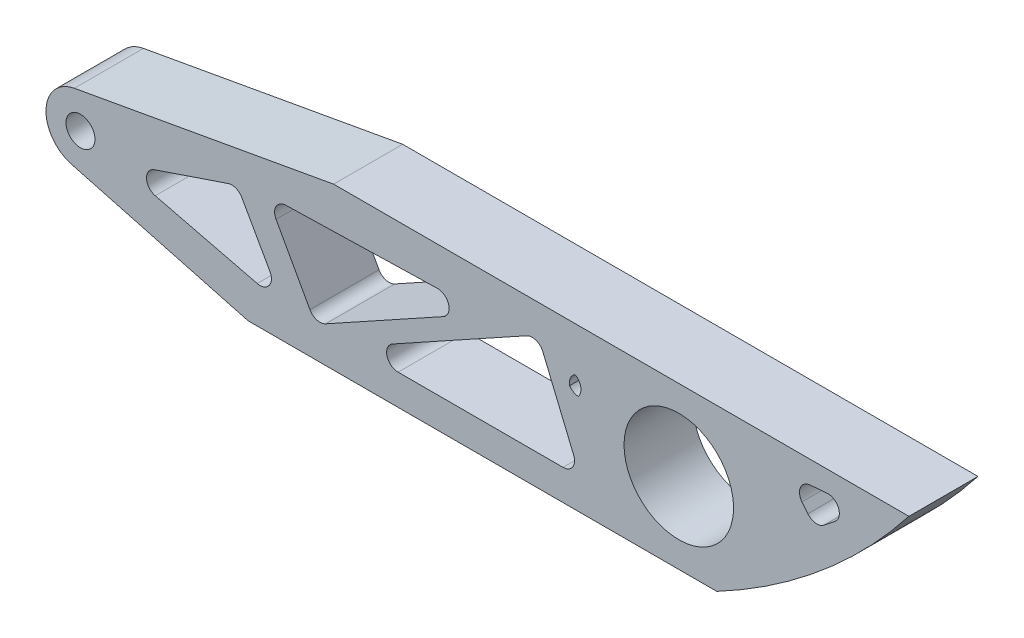
SolidWorks part; units mm, degrees
ref_plane "Front Plane" through (0, 0, 0) normal (0, 0, 1) x (1, 0, 0)
ref_plane "Top Plane" through (0, 0, 0) normal (0, 1, 0) x (1, 0, 0)
ref_plane "Right Plane" through (0, 0, 0) normal (1, 0, 0) x (0, 0, -1)
sketch "Sketch1" plane through (0, 0, 0) normal (0, 0, 1) x (1, 0, 0)
  line L1 (120.65, 22.225) -> (-120.65, 22.225)
  line L2 (120.65, 22.225) -> (120.65, -22.225)
  line L3 (120.65, -22.225) -> (-120.65, -22.225)
  line L4 (-120.65, 22.225) -> (-120.65, -22.225)
  line L5 (120.65, 22.225) -> (-120.65, -22.225) construction
  line L6 (120.65, -22.225) -> (-120.65, 22.225) construction
  point P0 (0, 0)
  dimension "D1" = 241.3
  dimension "D2" = 44.45
extrude "Boss-Extrude1" add sketch "Sketch1" along normal blind 19.06
sketch "Sketch3" plane through (0, 0, 19.06) normal (0, 0, 1) x (1, 0, 0)
  line L0 (0, 0) -> (-120.65, 0) construction
  line L1 (-120.65, 22.225) -> (-120.65, -22.225) construction
  circle A0 centre (-107.95, 0) radius 4
  dimension "D2" = 8
  dimension "D1" = 12.7
extrude "Cut-Extrude1" cut sketch "Sketch3" against normal through all
sketch "Sketch5" plane through (0, 0, 19.06) normal (0, 0, 1) x (1, 0, 0)
  line L0 (-120.65, -22.225) -> (120.65, -22.225) construction
  line L1 (-110.4107, -9.2017) -> (-61.7102, -22.225)
  line L2 (-109.6341, 9.3749) -> (-38.1, 22.225)
  line L3 (120.65, 22.225) -> (-120.65, 22.225) construction
  line L4 (-38.1, 22.225) -> (-120.65, 22.225)
  line L5 (-120.65, 22.225) -> (-120.65, -22.225)
  line L6 (-120.65, -22.225) -> (-61.7102, -22.225)
  line L7 (120.65, 22.225) -> (120.65, -22.225)
  line L8 (120.65, -22.225) -> (67.6371, -22.225)
  arc A0 (67.6371, -22.225) -> (120.65, 22.225) centre (-9.5799, 123.7049) ccw
  arc A2 (-109.6341, 9.3749) -> (-110.4107, -9.2017) centre (-107.95, 0) ccw
  point P15 (-38.5913, 22.225)
  line M3 (-120.65, 22.225) -> (-120.65, -22.225)
  line M4 (-120.65, -22.225) -> (120.65, -22.225)
  line M5 (120.65, -22.225) -> (120.65, 22.225)
  line M6 (120.65, 22.225) -> (-120.65, 22.225)
  dimension "D1" = 165.1
  dimension "D2" = 19.05
  dimension "D3" = 82.55
extrude "Cut-Extrude2" cut sketch "Sketch5" against normal through all contours A0 L8 M5 | A2 L2 L1 M6 M3 M4 region at (-86.3027, -16.6191, 19.06) region at (104.3043, -8.4634, 19.06)
sketch "Sketch6" plane through (0, 0, 19.06) normal (0, 0, 1) x (1, 0, 0)
  line L0 (-107.95, 0) -> (99.7595, 0) construction
  arc A0 (67.6371, -22.225) -> (120.65, 22.225) centre (-9.5799, 123.7049) ccw construction
sketch "Sketch11" plane through (0, 0, 0) normal (0, 0, -1) x (-1, 0, 0)
  line L1 (107.95, 0) -> (-99.7595, 0) construction
  circle A1 centre (-57.15, 0) radius 15.113
  circle A2 centre (107.95, 0) radius 4 construction
  dimension "D1" = 30.226
  dimension "D2" = 165.1
extrude "Cut-Extrude3" cut sketch "Sketch11" against normal through all
sketch "Sketch12" plane through (0, 0, 0) normal (0, 0, -1) x (-1, 0, 0)
  line L3 (62.1778, -29.4105) -> (46.0432, -22.2176)
  line L5 (46.0432, -22.2176) -> (70.9328, -9.772)
  line L6 (70.9328, -9.772) -> (62.1778, -29.4105)
  dimension "D1" = 90
extrude "Boss-Extrude2" [suppressed] add sketch "Sketch12" against normal up to surface (19.06 mm away)
sketch "Sketch14" plane through (0, 0, 19.06) normal (0, 0, 1) x (1, 0, 0)
  line L0 (87.4273, 15.5587) -> (94.742, 6.4153)
  line L1 (94.742, 6.4153) -> (108.4371, 17.3503)
  line L2 (108.4371, 17.3503) -> (87.4273, 15.5587)
  line L3 (18.2585, 14.338) -> (29.9735, -13.8007)
  line L5 (29.9735, -13.8007) -> (-32.6065, -13.8007)
  line L6 (-32.6065, -13.8007) -> (18.2585, 14.338)
  line L9 (-43.1009, -13.8007) -> (3.4683, 11.9615)
  line L10 (-64.7308, 8.6621) -> (-52.0681, -13.8007)
  line L11 (-52.0681, -13.8007) -> (-97.91, -2.5585)
  line L12 (-97.91, -2.5585) -> (-64.7308, 8.6621)
  line L14 (25.3772, 10.4563) -> (27.9586, 4.2561)
  line L15 (27.9586, 4.2561) -> (42.8511, 10.4563)
  line L16 (42.8511, 10.4563) -> (25.3772, 10.4563)
  line L17 (47.7718, 17.2115) -> (29.7305, 0) construction
  line L18 (-107.95, 0) -> (99.7595, 0) construction
  line L19 (29.7305, 0) -> (35.4762, -13.8007) construction
  line L23 (-43.1009, -13.8007) -> (-56.52, 10.4563)
  line L24 (-56.52, 10.4563) -> (3.4683, 11.9615)
  point P12 (-56.52, 10.4563)
  point P15 (-64.7308, 8.6621)
  point P22 (-52.0681, -13.8007)
  dimension "D1" = 8.9672
  dimension "D3" = 5.08
  dimension "D5" = 30.48
  dimension "D6" = 5.08
  dimension "D7" = 68.952
extrude "Cut-Extrude5" cut sketch "Sketch14" against normal through all
fillet "Fillet1" radius 3.175 15 edges at (-64.7308, 8.6621, 9.53) (-52.0681, -13.8007, 9.53) (-97.91, -2.5585, 9.53) (-56.52, 10.4563, 9.53) (3.4683, 11.9615, 9.53) (-43.1009, -13.8007, 9.53) (-32.6065, -13.8007, 9.53) (18.2585, 14.338, 9.53) (29.9735, -13.8007, 9.53) (87.4273, 15.5587, 9.53) (108.4371, 17.3503, 9.53) (94.742, 6.4153, 9.53) (27.9586, 4.2561, 9.53) (42.8511, 10.4563, 9.53) (25.3772, 10.4563, 9.53)
sketch "Sketch15" plane through (0, 0, 0) normal (0, 0, -1) x (-1, 0, 0)
  line L0 (61.7102, -22.225) -> (117.4667, -22.225) construction
  line L1 (117.4667, -22.225) -> (117.4667, 0.3979) construction
  arc A0 (110.4107, -9.2017) -> (109.6341, 9.3749) centre (107.95, 0) ccw construction
